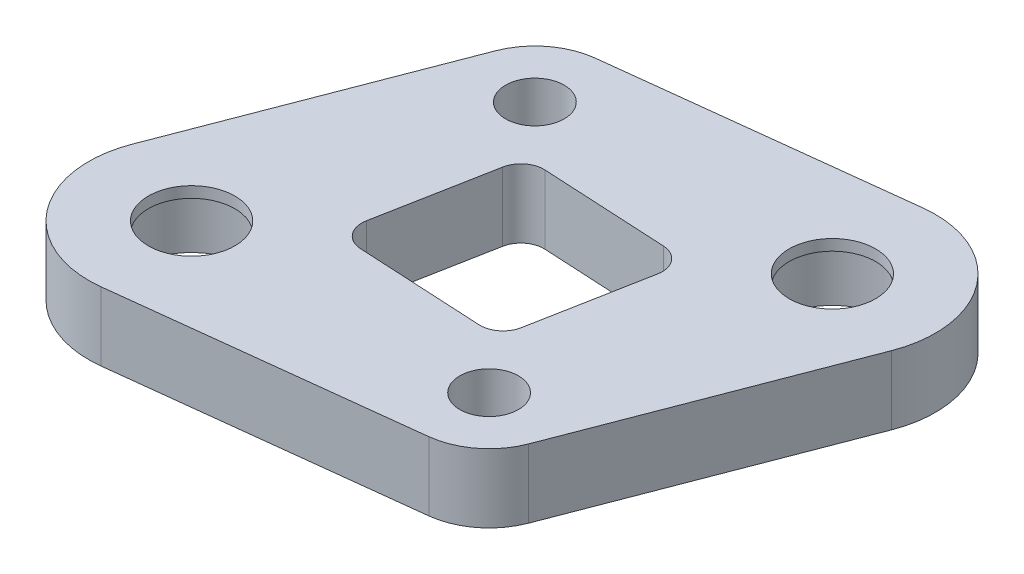
SolidWorks part; units mm, degrees
ref_plane "Front Plane" through (0, 0, 0) normal (0, 0, 1) x (1, 0, 0)
ref_plane "Top Plane" through (0, 0, 0) normal (0, 1, 0) x (1, 0, 0)
ref_plane "Right Plane" through (0, 0, 0) normal (1, 0, 0) x (0, 0, -1)
sketch "Sketch1" plane through (0, 0, 0) normal (0, 1, 0) x (1, 0, 0)
  line L0 (0, 0) -> (20.6375, 0) construction
  line L1 (20.6375, 0) -> (25.4, 19.05) construction
  line L2 (25.4, 19.05) -> (4.7625, 19.05) construction
  line L3 (4.7625, 19.05) -> (0, 0) construction
  line L8 (0.3164, 20.7568) -> (-6.6692, 2.5603)
  line L9 (4.213, 23.7807) -> (24.5757, 26.146)
  line L10 (32.0692, 16.4897) -> (25.0836, -1.7068)
  line L11 (0.8243, -7.096) -> (21.187, -4.7307)
  line L12 (0, 0) -> (25.4, 19.05) construction
  line L13 (4.7625, 19.05) -> (20.6375, 0) construction
  line L14 (7.5279, 4.1904) -> (16.2024, 3.7319)
  line L15 (17.8461, 5.0227) -> (19.3482, 12.9798)
  line L16 (17.8721, 14.8596) -> (9.1976, 15.3181)
  line L17 (7.5539, 14.0273) -> (6.0518, 6.0702)
  circle A0 centre (0, 0) radius 4.05
  circle A1 centre (25.4, 19.05) radius 4.05
  circle A2 centre (20.6375, 0) radius 2.032
  circle A3 centre (4.7625, 19.05) radius 2.032
  arc A4 (-6.6692, 2.5603) -> (0.8243, -7.096) centre (0, 0) ccw
  arc A5 (4.213, 23.7807) -> (0.3164, 20.7568) centre (4.7625, 19.05) ccw
  arc A6 (32.0692, 16.4897) -> (24.5757, 26.146) centre (25.4, 19.05) ccw
  arc A7 (21.187, -4.7307) -> (25.0836, -1.7068) centre (20.6375, 0) ccw
  arc A8 (7.5279, 4.1904) -> (6.0518, 6.0702) centre (7.6117, 5.7757) cw
  arc A9 (16.2024, 3.7319) -> (17.8461, 5.0227) centre (16.2862, 5.3172) ccw
  arc A10 (19.3482, 12.9798) -> (17.8721, 14.8596) centre (17.7883, 13.2743) ccw
  arc A11 (9.1976, 15.3181) -> (7.5539, 14.0273) centre (9.1138, 13.7328) ccw
  point P25 (5.715, 4.2863)
  point P28 (17.5886, 3.6587)
  point P31 (19.685, 14.7637)
  point P34 (7.8114, 15.3913)
  dimension "D4" = 8.1
  dimension "D5" = 4.064
  dimension "D6" = 7.1437
  dimension "D7" = 4.7625
  dimension "D12" = 1.5875
  dimension "D1" = 20.6375
  dimension "D2" = 19.05
  dimension "D3" = 4.7625
  dimension "D8" = 7.1437
  dimension "D9" = 7.1437
  dimension "D10" = 4.7625
  dimension "D11" = 4.7625
extrude "Boss-Extrude1" add sketch "Sketch1" along normal blind 4.7625
sketch "Sketch2" plane through (0, 4.7625, 0) normal (0, 1, 0) x (1, 0, 0)
  circle A0 centre (25.4, 19.05) radius 4.05 construction
  circle A1 centre (0, 0) radius 4.05 construction
  circle A2 centre (25.4, 19.05) radius 4.05
  circle A3 centre (0, 0) radius 4.05
  circle A4 centre (25.4, 19.05) radius 3
  circle A5 centre (0, 0) radius 3
  point P8 (0, 0)
  dimension "D1" = 6
extrude "Boss-Extrude2" add sketch "Sketch2" against normal blind 0.7625
equation "\"D9@Sketch1\"=\"D8@Sketch1\""
equation "\"D11@Sketch1\"=\"D10@Sketch1\""
